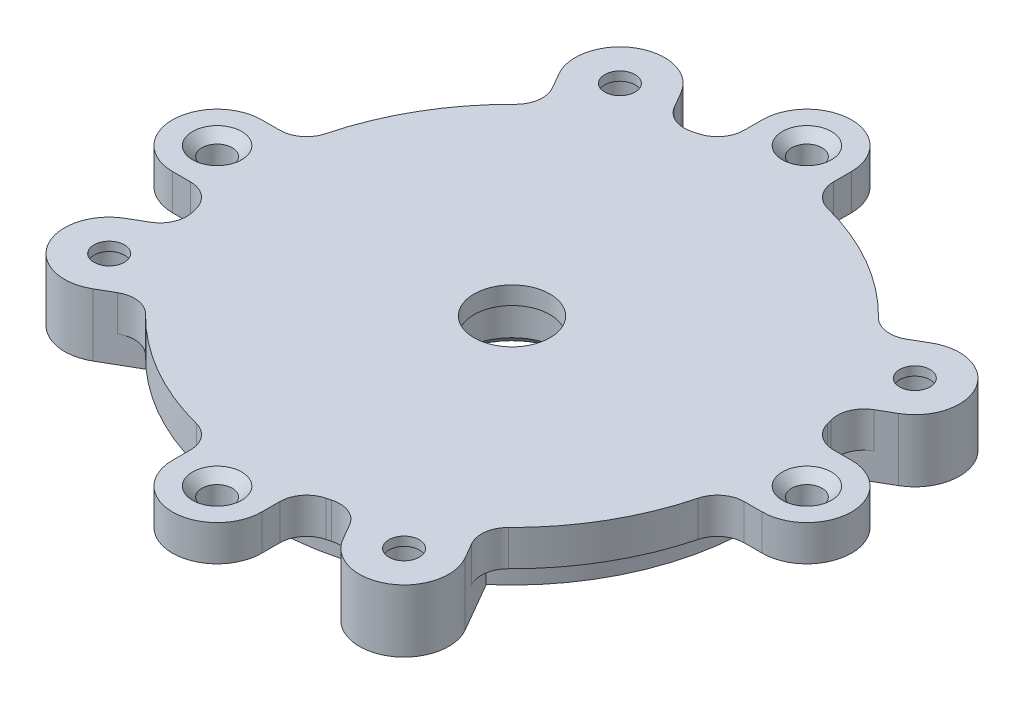
SolidWorks part; units mm, degrees
note: The reader was unsure of these and kept them because the rebuilt part matched: shared geometry of "Esquisse2<2>".
ref_plane "Plan de face" through (0, 0, 0) normal (0, 0, 1) x (1, 0, 0)
ref_plane "Plan de dessus" through (0, 0, 0) normal (0, 1, 0) x (1, 0, 0)
ref_plane "Plan de droite" through (0, 0, 0) normal (1, 0, 0) x (0, 0, -1)
sketch "Sketch1" plane through (0, 0, 0) normal (0, 0, 1) x (1, 0, 0)
  line L0 (0, 16.3186) -> (0, -12.1553) construction
  line L1 (6.5, 0) -> (27, 0)
  line L2 (27, 0) -> (27, 3)
  line L3 (27, 3) -> (29, 3)
  line L4 (29, 3) -> (29, 7)
  line L5 (29, 7) -> (4.25, 7)
  line L7 (4.25, 7) -> (4.25, 5)
  line L8 (4.25, 5) -> (5.5, 5)
  line L9 (5.5, 5) -> (5.5, 1)
  line L10 (5.5, 1) -> (6.5, 0)
  dimension "D1" = 29
  dimension "D2" = 27
  dimension "D3" = 3
  dimension "D4" = 4
  dimension "D5" = 4
  dimension "D6" = 1
  dimension "D7" = 45
  dimension "D8" = 5.5
  dimension "D9" = 4.25
revolve "Revolve1" add sketch "Sketch1" angle 360 about L0
sketch "Esquisse1" plane through (0, 7, 0) normal (0, 1, 0) x (1, 0, 0)
  line L0 (0, 0) -> (0, 33) construction
  line L1 (-5, 33) -> (-5, 28.5657)
  line L2 (5, 33) -> (5, 28.5657)
  circle A0 centre (0, 33) radius 1.7
  arc A1 (5, 33) -> (-5, 33) centre (0, 33) ccw
  circle A2 centre (0, 0) radius 29 construction
  arc A3 (-5, 28.5657) -> (5, 28.5657) centre (0, 0) cw
  dimension "D1" = 33
  dimension "D2" = 10
  dimension "D3" = 3.4
extrude "Boss.-Extru.1" add sketch "Esquisse1" against normal up to surface (4 mm away) up to face at (0, 3, 29)
fillet "Congé1" radius 3 2 edges at (5, 5, -28.5657) (-5, 5, -28.5657)
pattern_circular "Répétition circulaire1" count 4 over 360 about axis through (0, 0, 0) along (0, 1, 0) of "Boss.-Extru.1", "Congé1"
chamfer "Chanfrein1" distance 1.05 angle 45 4 edges at (0, 7, -31.3) (31.3, 7, 0) (0, 7, 31.3) (-31.3, 7, 0)
sketch "Esquisse2" plane through (0, 7, 0) normal (0, 1, 0) x (1, 0, 0)
  line L0 (0, 0) -> (7.5058, 28.0118) construction
  line L1 (0, 0) -> (0, 38) construction
  line L2 (0, 0) -> (-14.5, 25.1147) construction
  line L3 (0, 0) -> (-25.1147, -14.5) construction
  line L4 (0, 0) -> (25.1147, 14.5) construction
  line L5 (0, 0) -> (14.5, -25.1147) construction
  line L6 (-14.5, 25.1147) -> (-16.5, 28.5788) construction
  line L7 (25.1147, 14.5) -> (28.5788, 16.5) construction
  line L8 (14.5, -25.1147) -> (16.5, -28.5788) construction
  line L9 (-25.1147, -14.5) -> (-28.5788, -16.5) construction
  line L10 (-12.1699, 31.0788) -> (-8.9364, 25.4783)
  line L11 (-20.8301, 26.0788) -> (-17.5966, 20.4783)
  line L12 (31.0788, 12.1699) -> (25.4783, 8.9364)
  line L13 (20.8301, -26.0788) -> (17.5966, -20.4783)
  line L14 (12.1699, -31.0788) -> (8.9364, -25.4783)
  line L15 (-26.0788, -20.8301) -> (-20.4783, -17.5966)
  line L16 (-31.0788, -12.1699) -> (-25.4783, -8.9364)
  line L17 (26.0788, 20.8301) -> (20.4783, 17.5966)
  arc A0 (28.0791, 7.25) -> (7.25, 28.0791) centre (0, 0) ccw construction
  arc A1 (5, 33) -> (-5, 33) centre (0, 33) ccw construction
  arc A2 (-7.25, 28.0791) -> (-28.0791, 7.25) centre (0, 0) ccw construction
  arc A4 (7.25, -28.0791) -> (28.0791, -7.25) centre (0, 0) ccw construction
  circle A5 centre (-16.5, 28.5788) radius 2.4
  circle A6 centre (28.5788, 16.5) radius 2.4
  circle A7 centre (16.5, -28.5788) radius 2.4
  circle A8 centre (-28.5788, -16.5) radius 2.4
  arc A9 (-28.0791, -7.25) -> (-7.25, -28.0791) centre (0, 0) ccw construction
  arc A10 (-12.1699, 31.0788) -> (-20.8301, 26.0788) centre (-16.5, 28.5788) ccw
  arc A11 (31.0788, 12.1699) -> (26.0788, 20.8301) centre (28.5788, 16.5) ccw
  arc A12 (12.1699, -31.0788) -> (20.8301, -26.0788) centre (16.5, -28.5788) ccw
  arc A13 (-31.0788, -12.1699) -> (-26.0788, -20.8301) centre (-28.5788, -16.5) ccw
  circle A20 centre (0, 0) radius 27 construction
  arc A21 (-8.9364, 25.4783) -> (-17.5966, 20.4783) centre (0, 0) ccw
  circle A22 centre (0, 0) radius 27 construction
  arc A23 (25.4783, 8.9364) -> (20.4783, 17.5966) centre (0, 0) ccw
  arc A24 (8.9364, -25.4783) -> (17.5966, -20.4783) centre (0, 0) ccw
  arc A25 (-25.4783, -8.9364) -> (-20.4783, -17.5966) centre (0, 0) ccw
  point P18 (-24.603, -11.1216)
  point P29 (-18.8673, -19.3139)
  point P41 (26.1603, 6.6814)
  point P42 (15.2259, -22.2974)
  point P43 (21.934, 15.7448)
  point P48 (22.2971, -15.2263)
  point P50 (-18.8667, 19.3145)
  point P54 (-24.6024, 11.1229)
  dimension "D6" = 33
  dimension "D7" = 4.8
  dimension "D8" = 5
  dimension "D1" = 15
  dimension "D2" = 45
  dimension "D3" = 45
  dimension "D4" = 90
  dimension "D5" = 90
extrude "Boss.-Extru.2" add sketch "Esquisse2" against normal up to surface (7 mm away) up to face at (0, 0, 27)
fillet "Congé2" radius 3 8 edges at (-18.613, 5, -22.2386) (-9.9527, 5, -27.2386) (22.2386, 5, -18.613) (27.2386, 5, -9.9527) (18.613, 5, 22.2386) (9.9527, 5, 27.2386) (-22.2386, 5, 18.613) (-27.2386, 5, 9.9527)
extrude "Boss.-Extru.3" add sketch "Esquisse2<2>" against normal blind 1 contours A7 | A6 | A5 | A8
sketch "Esquisse2<2>" plane through (0, 7, 0) normal (0, 1, 0) x (1, 0, 0) same geometry as "Esquisse2"
sketch "Esquisse5" plane through (0, 7, 0) normal (0, 1, 0) x (1, 0, 0)
  point P0 (16.5, -28.5788)
  point P3 (28.5788, 16.5)
  point P6 (-16.5, 28.5788)
  point P9 (-28.5788, -16.5)
hole_wizard "M3 Clearance Hole1" positions "Esquisse5" profile "Esquisse4" hole size "M3" standard "ANSI Metric" end condition through all
sketch "Esquisse4" plane through (16.5, 7, 28.5788) normal (1, 0, 0) x (0, 0, 1)
  line L0 (0, 0) -> (0, 7)
  line L1 (0, 7) -> (1.7, 7)
  line L2 (1.7, 7) -> (1.7, 0)
  line L5 (1.7, 0) -> (0, 0)
  line L11 (0, -6.35) -> (0, 107.95) construction
  dimension "Thru Hole Dia." = 3.4
  dimension "Thru Hole Depth" = 7
chamfer "Chanfrein2" distance 0.5 angle 45 4 edges at (16.5, 0, 30.9788) (28.5788, 0, -14.1) (-16.5, 0, -26.1788) (-28.5788, 0, 18.9)
